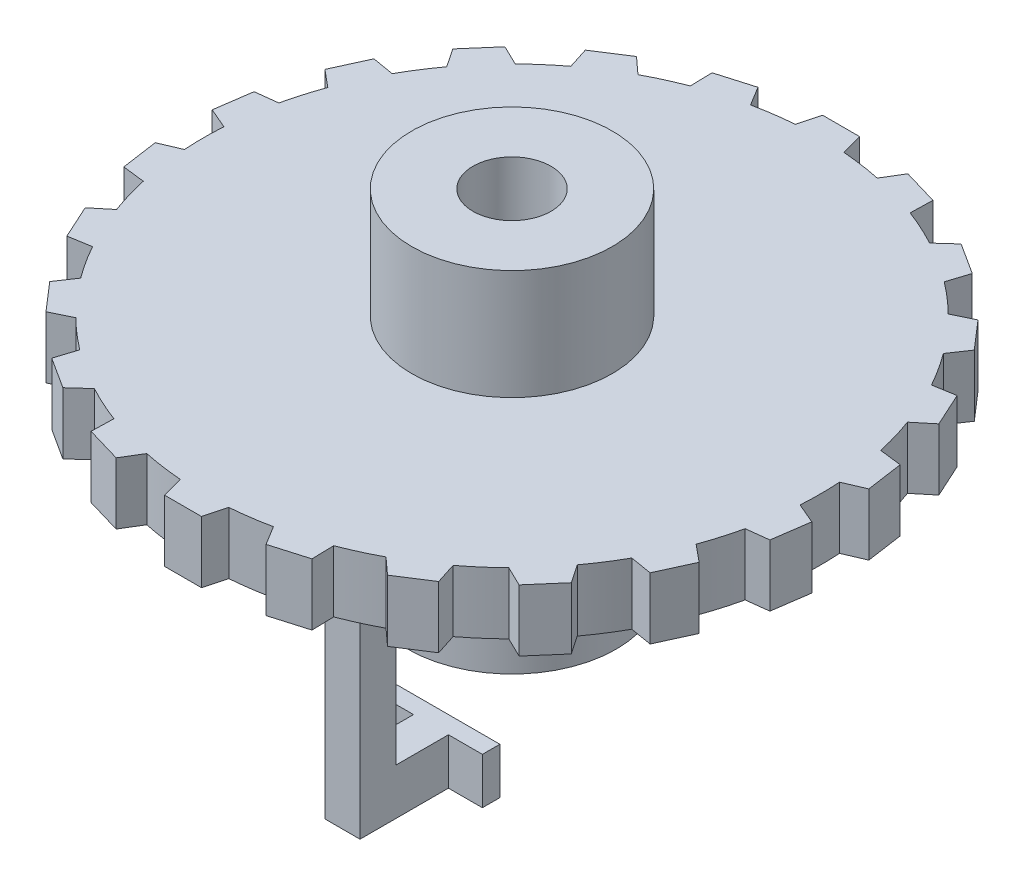
SolidWorks part; units mm, degrees
ref_plane "Front Plane" through (0, 0, 0) normal (0, 0, 1) x (1, 0, 0)
ref_plane "Top Plane" through (0, 0, 0) normal (0, 1, 0) x (1, 0, 0)
ref_plane "Right Plane" through (0, 0, 0) normal (1, 0, 0) x (0, 0, -1)
sketch "Sketch1" plane through (0, 0, 0) normal (0, 1, 0) x (1, 0, 0)
  circle A0 centre (0, 0) radius 30
  dimension "D1" = 60
extrude "Boss-Extrude3" add sketch "Sketch1" along normal blind 6
sketch "Sketch2" plane through (0, 6, 0) normal (0, 1, 0) x (1, 0, 0)
  line L0 (0, 0) -> (0, 62.0758) construction
  line L1 (0, 32) -> (1.8, 32)
  line L2 (1.8, 32) -> (3.1412, 26.9947)
  line L3 (3.1412, 26.9947) -> (0, 26.9947)
  line L4 (0, 26.9947) -> (-3.1412, 26.9947)
  line L5 (-3.1412, 26.9947) -> (-1.8, 32)
  line L6 (-1.8, 32) -> (0, 32)
  dimension "D1" = 1.8
  dimension "D2" = 1.8
  dimension "D3" = 75
  dimension "D4" = 75
  dimension "D5" = 32
extrude "Boss-Extrude2" add sketch "Sketch2" against normal blind 6
pattern_circular "CirPattern3" count 22 over 360 about axis through (0, 6, 0) along (0, -1, 0) of "Boss-Extrude2"
sketch "Sketch5" plane through (0, 6, 0) normal (0, 1, 0) x (1, 0, 0)
  circle A0 centre (0, 0) radius 9.75
  dimension "D1" = 19.5
extrude "Boss-Extrude4" add sketch "Sketch5" along normal blind 10.7
sketch "Sketch6" plane through (0, 16.7, 0) normal (0, 1, 0) x (1, 0, 0)
  circle A0 centre (0, 0) radius 3.8
  dimension "D1" = 7.6
extrude "Cut-Extrude1" cut sketch "Sketch6" against normal through all
sketch "Sketch7" plane through (0, 0, 0) normal (0, -1, 0) x (1, 0, 0)
  circle A0 centre (0, 0) radius 10.15
  dimension "D1" = 20.3
extrude "Boss-Extrude5" add sketch "Sketch7" along normal blind 17
sketch "Sketch8" plane through (0, -17, 0) normal (0, -1, 0) x (1, 0, 0)
  circle A0 centre (0, 0) radius 7.25
  dimension "D1" = 14.5
extrude "Cut-Extrude2" cut sketch "Sketch8" against normal blind 17
sketch "Sketch9" plane through (0, 0, 0) normal (0, 0, 1) x (1, 0, 0)
  line L1 (-2.3523, -1.9171) -> (1.6477, -1.9171)
  line L2 (-2.3523, -1.9171) -> (-2.3523, -5.9171)
  line L3 (-2.3523, -5.9171) -> (1.6477, -5.9171)
  line L4 (1.6477, -1.9171) -> (1.6477, -5.9171)
  line L5 (-2.3523, -1.9171) -> (1.6477, -5.9171) construction
  line L6 (-2.3523, -5.9171) -> (1.6477, -1.9171) construction
  point P0 (-0.3523, -3.9171)
  dimension "D1" = 4
  dimension "D2" = 4
sketch3d "3DSketch1"
  line L1 (-2.0296, -4.3245, 10.15) -> (1.3699, -4.3245, 10.15)
  line L2 (-2.0296, -4.3245, 10.15) -> (-2.0296, -9.091, 10.15)
  line L3 (-2.0296, -9.091, 10.15) -> (1.3699, -9.091, 10.15)
  line L4 (1.3699, -4.3245, 10.15) -> (1.3699, -9.091, 10.15)
  line L5 (-2.0296, -4.3245, 10.15) -> (1.3699, -9.091, 10.15) construction
  line L6 (-2.0296, -9.091, 10.15) -> (1.3699, -4.3245, 10.15) construction
  point P0 (-0.3298, -6.7078, 10.15)
extrude "Boss-Extrude6" add sketch "3DSketch1" along direction (0, 0, 1) on the side of the normal blind 6 separate body contours L4 L3 L2 L1
sketch "Sketch10" plane through (0, 0, 16.15) normal (0, 0, 1) x (1, 0, 0)
  line L1 (1.3699, -4.3245) -> (-2.0296, -4.3245)
  line L2 (1.3699, -4.3245) -> (1.3699, -29.3245)
  line L3 (1.3699, -29.3245) -> (-2.0296, -29.3245)
  line L4 (-2.0296, -4.3245) -> (-2.0296, -29.3245)
  dimension "D1" = 25
extrude "Boss-Extrude7" add sketch "Sketch10" against normal blind 3.5
sketch "Sketch11" plane through (0, 0, 12.65) normal (0, 0, -1) x (-1, 0, 0)
  line L0 (-1.3699, -29.3245) -> (-1.3699, -9.091) construction
  line L1 (2.0296, -29.3245) -> (-1.3699, -29.3245)
  line L2 (2.0296, -29.3245) -> (2.0296, -24.8245)
  line L3 (2.0296, -24.8245) -> (-1.3699, -24.8245)
  line L4 (-1.3699, -29.3245) -> (-1.3699, -24.8245)
  dimension "D1" = 4.5
extrude "Boss-Extrude8" add sketch "Sketch11" along normal blind 5.1
sketch "Sketch12" plane through (0, 0, 7.55) normal (0, 0, -1) x (-1, 0, 0)
  line L0 (-1.3699, -24.8245) -> (2.0296, -29.3245) construction
  line L2 (-4.6702, -24.8245) -> (5.3298, -24.8245)
  line L3 (-4.6702, -24.8245) -> (-4.6702, -29.3245)
  line L4 (-4.6702, -29.3245) -> (5.3298, -29.3245)
  line L5 (5.3298, -24.8245) -> (5.3298, -29.3245)
  line L6 (-4.6702, -24.8245) -> (5.3298, -29.3245) construction
  line L7 (-4.6702, -29.3245) -> (5.3298, -24.8245) construction
  point P4 (0.3298, -27.0745)
  dimension "D1" = 10
extrude "Boss-Extrude9" add sketch "Sketch12" along normal blind 1.7
sketch "Sketch13" plane through (0, 0, 16.15) normal (0, 0, 1) x (1, 0, 0)
  line L0 (1.3699, -4.3245) -> (3.3699, -4.3245) construction
  line L2 (3.3699, -4.3245) -> (5.8699, -4.3245)
  line L3 (3.3699, -4.3245) -> (3.3699, -6.8245)
  line L4 (3.3699, -6.8245) -> (5.8699, -6.8245)
  line L5 (5.8699, -4.3245) -> (5.8699, -6.8245)
  dimension "D1" = 2.5
  dimension "D2" = 2.5
  dimension "D3" = 2
extrude "Cut-Extrude3" cut sketch "Sketch13" against normal through all
